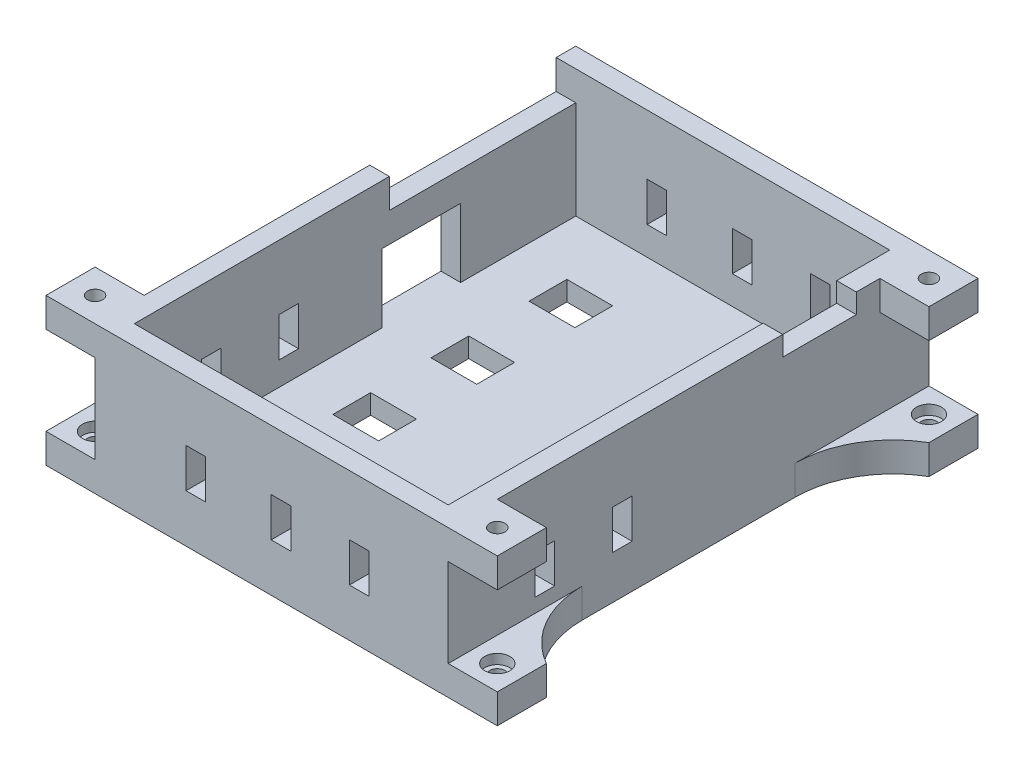
SolidWorks part; units mm, degrees
ref_plane "Спереди" through (0, 0, 0) normal (0, 0, 1) x (1, 0, 0)
ref_plane "Сверху" through (0, 0, 0) normal (0, 1, 0) x (1, 0, 0)
ref_plane "Справа" through (0, 0, 0) normal (1, 0, 0) x (0, 0, -1)
sketch "Sketch1" plane through (0, 0, 0) normal (0, 1, 0) x (1, 0, 0)
  line L1 (-13.614, 19.3684) -> (22.386, 19.3684)
  line L2 (-13.614, 19.3684) -> (-13.614, -29.6316)
  line L3 (-13.614, -29.6316) -> (22.386, -29.6316)
  line L4 (22.386, 19.3684) -> (22.386, -29.6316)
  dimension "D1" = 36
  dimension "D2" = 49
extrude "Boss-Extrude1" add sketch "Sketch1" along normal blind 2
sketch "Sketch2" plane through (0, 2, 0) normal (0, 1, 0) x (1, 0, 0)
  line L1 (-11.614, 17.3684) -> (20.386, 17.3684)
  line L2 (-11.614, 17.3684) -> (-11.614, -27.6316)
  line L3 (-11.614, -27.6316) -> (20.386, -27.6316)
  line L4 (20.386, 17.3684) -> (20.386, -27.6316)
  line L5 (-13.614, 19.3684) -> (22.386, 19.3684)
  line L6 (-13.614, 19.3684) -> (-13.614, -29.6316)
  line L7 (-13.614, -29.6316) -> (22.386, -29.6316)
  line L8 (22.386, 19.3684) -> (22.386, -29.6316)
  dimension "D1" = 2
  dimension "D2" = 2
  dimension "D3" = 2
  dimension "D4" = 2
extrude "Boss-Extrude2" add sketch "Sketch2" along normal blind 13
sketch "Sketch3" plane through (20.386, 0, 0) normal (-1, 0, 0) x (0, 0, 1)
  line L0 (27.6316, 15) -> (-17.3684, 15) construction
  line L1 (-11.9684, 15) -> (-4.4684, 15)
  line L2 (-11.9684, 15) -> (-11.9684, 13)
  line L3 (-11.9684, 13) -> (-4.4684, 13)
  line L4 (-4.4684, 15) -> (-4.4684, 13)
  line L5 (-17.3684, 15) -> (-17.3684, 2) construction
  dimension "D1" = 7.5
  dimension "D2" = 5.4
  dimension "D3" = 2
extrude "Cut-Extrude1" cut sketch "Sketch3" against normal through all and the other way blind 5
sketch "Sketch4" plane through (0, 0, 0) normal (0, -1, 0) x (1, 0, 0)
  line L0 (4.386, 29.6316) -> (4.386, -19.3684) construction
  line L1 (-13.614, 29.6316) -> (22.386, 29.6316) construction
  line L2 (22.386, -19.3684) -> (-13.614, -19.3684) construction
  line L3 (9.5173, 22.5248) -> (14.1877, 22.5248)
  line L4 (-6.4827, 22.5248) -> (-1.8123, 22.5248)
  line L5 (-6.4827, 22.5248) -> (-6.4827, 18.6717)
  line L6 (-6.4827, 18.6717) -> (-1.8123, 18.6717)
  line L7 (-1.8123, 22.5248) -> (-1.8123, 18.6717)
  line L8 (14.1877, 22.5248) -> (14.1877, 18.6717)
  line L9 (9.5173, 18.6717) -> (14.1877, 18.6717)
  line L10 (9.5173, 22.5248) -> (9.5173, 18.6717)
  line L11 (9.5173, 12.5248) -> (14.1877, 12.5248)
  line L12 (14.1877, 12.5248) -> (14.1877, 8.6717)
  line L13 (9.5173, 8.6717) -> (14.1877, 8.6717)
  line L14 (9.5173, 12.5248) -> (9.5173, 8.6717)
  line L15 (9.5173, 2.5248) -> (14.1877, 2.5248)
  line L16 (14.1877, 2.5248) -> (14.1877, -1.3283)
  line L17 (9.5173, -1.3283) -> (14.1877, -1.3283)
  line L18 (9.5173, 2.5248) -> (9.5173, -1.3283)
  line L19 (9.5173, -7.4752) -> (14.1877, -7.4752)
  line L20 (14.1877, -7.4752) -> (14.1877, -11.3283)
  line L21 (9.5173, -11.3283) -> (14.1877, -11.3283)
  line L22 (9.5173, -7.4752) -> (9.5173, -11.3283)
  line L23 (-6.4827, 12.5248) -> (-1.8123, 12.5248)
  line L24 (-1.8123, 12.5248) -> (-1.8123, 8.6717)
  line L25 (-6.4827, 8.6717) -> (-1.8123, 8.6717)
  line L26 (-6.4827, 12.5248) -> (-6.4827, 8.6717)
  line L27 (-6.4827, 2.5248) -> (-1.8123, 2.5248)
  line L28 (-1.8123, 2.5248) -> (-1.8123, -1.3283)
  line L29 (-6.4827, -1.3283) -> (-1.8123, -1.3283)
  line L30 (-6.4827, 2.5248) -> (-6.4827, -1.3283)
  line L31 (-6.4827, -7.4752) -> (-1.8123, -7.4752)
  line L32 (-1.8123, -7.4752) -> (-1.8123, -11.3283)
  line L33 (-6.4827, -11.3283) -> (-1.8123, -11.3283)
  line L34 (-6.4827, -7.4752) -> (-6.4827, -11.3283)
  dimension "D1" = 2
  dimension "D2" = 4
extrude "Cut-Extrude2" cut sketch "Sketch4" against normal through all
sketch "Sketch10" plane through (0, 15, 0) normal (0, 1, 0) x (1, 0, 0)
  line L0 (-13.614, 19.3684) -> (-13.614, -29.6316) construction
  line L1 (-11.614, 17.3684) -> (-13.614, 17.3684)
  line L2 (-11.614, 17.3684) -> (-11.614, -1.6316)
  line L3 (-11.614, -1.6316) -> (-13.614, -1.6316)
  line L4 (-13.614, 17.3684) -> (-13.614, -1.6316)
  dimension "D1" = 19
extrude "Cut-Extrude6" cut sketch "Sketch10" against normal blind 3
sketch "Sketch11" plane through (-13.614, 0, 0) normal (-1, 0, 0) x (0, 0, 1)
  line L0 (-19.3684, 0) -> (29.6316, 0) construction
  line L1 (-5.6344, 2) -> (2.3656, 2)
  line L2 (-5.6344, 2) -> (-5.6344, 9)
  line L3 (-5.6344, 9) -> (2.3656, 9)
  line L4 (2.3656, 2) -> (2.3656, 9)
  dimension "D1" = 7
  dimension "D2" = 8
  dimension "D3" = 2
extrude "Cut-Extrude7" cut sketch "Sketch11" against normal blind 2
sketch "Sketch12" plane through (-13.614, 0, 0) normal (-1, 0, 0) x (0, 0, 1)
  line L1 (-19.3684, 0) -> (-14.3684, 0)
  line L2 (-19.3684, 0) -> (-19.3684, 3)
  line L3 (-19.3684, 3) -> (-14.3684, 3)
  line L4 (-14.3684, 0) -> (-14.3684, 3)
  line L5 (29.6316, 15) -> (24.6316, 15)
  line L6 (29.6316, 15) -> (29.6316, 12)
  line L7 (29.6316, 12) -> (24.6316, 12)
  line L8 (24.6316, 15) -> (24.6316, 12)
  line L9 (29.6316, 0) -> (24.6316, 0)
  line L10 (29.6316, 0) -> (29.6316, 3)
  line L11 (29.6316, 3) -> (24.6316, 3)
  line L12 (24.6316, 0) -> (24.6316, 3)
  dimension "D1" = 5
  dimension "D2" = 3
extrude "Boss-Extrude3" add sketch "Sketch12" along normal blind 5
sketch "Sketch13" plane through (22.386, 0, 0) normal (1, 0, 0) x (0, 0, -1)
  line L1 (19.3684, 0) -> (14.3684, 0)
  line L2 (19.3684, 0) -> (19.3684, 3)
  line L3 (19.3684, 3) -> (14.3684, 3)
  line L4 (14.3684, 0) -> (14.3684, 3)
  line L9 (-29.6316, 15) -> (-24.6316, 15)
  line L10 (-29.6316, 15) -> (-29.6316, 12)
  line L11 (-29.6316, 12) -> (-24.6316, 12)
  line L12 (-24.6316, 15) -> (-24.6316, 12)
  line L13 (-29.6316, 0) -> (-24.6316, 0)
  line L14 (-29.6316, 0) -> (-29.6316, 3)
  line L15 (-29.6316, 3) -> (-24.6316, 3)
  line L16 (-24.6316, 0) -> (-24.6316, 3)
  line L17 (19.3684, 15) -> (14.3684, 15)
  line L18 (19.3684, 15) -> (19.3684, 12)
  line L19 (19.3684, 12) -> (14.3684, 12)
  line L20 (14.3684, 15) -> (14.3684, 12)
  dimension "D1" = 3
  dimension "D2" = 5
extrude "Boss-Extrude4" add sketch "Sketch13" along normal blind 5
sketch "Sketch14" plane through (0, 0, 0) normal (0, -1, 0) x (1, 0, 0)
  line L0 (27.386, -19.3684) -> (-18.614, -19.3684) construction
  line L1 (27.386, -14.3684) -> (27.386, -19.3684) construction
  line L3 (-18.614, -19.3684) -> (-18.614, -14.3684) construction
  line L5 (-18.614, 29.6316) -> (27.386, 29.6316) construction
  circle A0 centre (24.886, -16.8684) radius 0.775
  circle A1 centre (-16.114, -16.8684) radius 0.775
  circle A2 centre (-16.114, 27.1316) radius 0.775
  circle A3 centre (24.886, 27.1316) radius 0.775
  dimension "D6" = 1.55
  dimension "D1" = 2.5
  dimension "D2" = 2.5
  dimension "D3" = 2.5
  dimension "D4" = 2.5
  dimension "D5" = 2.5
extrude "Cut-Extrude8" cut sketch "Sketch14" against normal through all
sketch "Sketch15" plane through (0, 3, 0) normal (0, 1, 0) x (1, 0, 0)
  circle A0 centre (24.886, 16.8684) radius 1.275
  circle A1 centre (24.886, -27.1316) radius 1.275
  circle A2 centre (-16.114, -27.1316) radius 1.275
  circle A3 centre (-16.114, 16.8684) radius 1.275
  dimension "D1" = 2.55
extrude "Cut-Extrude9" cut sketch "Sketch15" against normal blind 1
sketch "Sketch16" plane through (0, 12, 0) normal (0, -1, 0) x (1, 0, 0)
  circle A0 centre (-16.114, 27.1316) radius 1.275
  circle A1 centre (24.886, 27.1316) radius 1.275
  circle A2 centre (24.886, -16.8684) radius 1.275
  dimension "D1" = 2.55
extrude "Cut-Extrude10" cut sketch "Sketch16" against normal blind 1
fillet "Fillet2" radius 10 4 edges at (-13.614, 1.5, -14.3684) (22.386, 1.5, -14.3684) (22.386, 1.5, 24.6316) (-13.614, 1.5, 24.6316)
sketch "Sketch17" plane through (0, 0, 29.6316) normal (0, 0, 1) x (1, 0, 0)
  line L1 (-4.3402, 8.8945) -> (-2.3402, 8.8945)
  line L2 (-4.3402, 8.8945) -> (-4.3402, 4.8945)
  line L3 (-4.3402, 4.8945) -> (-2.3402, 4.8945)
  line L4 (-2.3402, 8.8945) -> (-2.3402, 4.8945)
  line L5 (4.3432, 8.8945) -> (6.3432, 8.8945)
  line L6 (4.3432, 8.8945) -> (4.3432, 4.8945)
  line L7 (4.3432, 4.8945) -> (6.3432, 4.8945)
  line L8 (6.3432, 8.8945) -> (6.3432, 4.8945)
  line L9 (12.3095, 8.8945) -> (14.3095, 8.8945)
  line L10 (12.3095, 8.8945) -> (12.3095, 4.8945)
  line L11 (12.3095, 4.8945) -> (14.3095, 4.8945)
  line L12 (14.3095, 8.8945) -> (14.3095, 4.8945)
  dimension "D1" = 2
  dimension "D2" = 4
extrude "Cut-Extrude11" cut sketch "Sketch17" against normal through all
sketch "Sketch18" plane through (-13.614, 0, 0) normal (-1, 0, 0) x (0, 0, 1)
  line L1 (10.8938, 8.4242) -> (12.8938, 8.4242)
  line L2 (10.8938, 8.4242) -> (10.8938, 4.4242)
  line L3 (10.8938, 4.4242) -> (12.8938, 4.4242)
  line L4 (12.8938, 8.4242) -> (12.8938, 4.4242)
  line L5 (18.7843, 8.4242) -> (20.7843, 8.4242)
  line L6 (18.7843, 8.4242) -> (18.7843, 4.4242)
  line L7 (18.7843, 4.4242) -> (20.7843, 4.4242)
  line L8 (20.7843, 8.4242) -> (20.7843, 4.4242)
  dimension "D1" = 2
  dimension "D2" = 4
extrude "Cut-Extrude12" cut sketch "Sketch18" against normal through all
sketch "Sketch19" plane through (0, 15, 0) normal (0, 1, 0) x (1, 0, 0)
  line L0 (20.386, 17.3684) -> (-13.614, 17.3684) construction
  line L1 (-13.614, 19.3684) -> (23.4688, 19.3684)
  line L2 (-13.614, 19.3684) -> (-13.614, 17.3684)
  line L3 (-13.614, 17.3684) -> (23.4688, 17.3684)
  line L4 (23.4688, 19.3684) -> (23.4688, 17.3684)
extrude "Cut-Extrude13" cut sketch "Sketch19" against normal blind 2
sketch "Sketch20" plane through (0, 13, 0) normal (0, 1, 0) x (1, 0, 0)
  line L1 (-13.614, 19.3684) -> (23.4688, 19.3684)
  line L2 (-13.614, 19.3684) -> (-13.614, 17.3684)
  line L3 (-13.614, 17.3684) -> (23.4688, 17.3684)
  line L4 (23.4688, 19.3684) -> (23.4688, 17.3684)
extrude "Boss-Extrude5" add sketch "Sketch20" along normal blind 2
sketch "Sketch21" plane through (0, 15, 0) normal (0, 1, 0) x (1, 0, 0)
  line L0 (-18.614, -29.6316) -> (27.386, -29.6316) construction
  line L1 (-11.614, -1.6316) -> (-13.614, -1.6316)
  line L2 (-11.614, -1.6316) -> (-11.614, -29.6316)
  line L3 (-11.614, -29.6316) -> (-13.614, -29.6316)
  line L4 (-13.614, -1.6316) -> (-13.614, -29.6316)
extrude "Cut-Extrude14" cut sketch "Sketch21" against normal blind 2
sketch "Sketch22" plane through (0, 13, 0) normal (0, 1, 0) x (1, 0, 0)
  line L1 (-13.614, -1.6316) -> (-11.614, -1.6316)
  line L2 (-13.614, -1.6316) -> (-13.614, -29.6316)
  line L3 (-13.614, -29.6316) -> (-11.614, -29.6316)
  line L4 (-11.614, -1.6316) -> (-11.614, -29.6316)
extrude "Boss-Extrude6" add sketch "Sketch22" along normal blind 2
sketch "Sketch23" plane through (0, 15, 0) normal (0, 1, 0) x (1, 0, 0)
  line L0 (-18.614, -29.6316) -> (27.386, -29.6316) construction
  line L1 (20.386, 4.4684) -> (22.386, 4.4684)
  line L2 (20.386, 4.4684) -> (20.386, -29.6316)
  line L3 (20.386, -29.6316) -> (22.386, -29.6316)
  line L4 (22.386, 4.4684) -> (22.386, -29.6316)
extrude "Cut-Extrude16" cut sketch "Sketch23" against normal blind 1.5
sketch "Sketch24" plane through (0, 13.5, 0) normal (0, 1, 0) x (1, 0, 0)
  line L0 (20.386, -29.6316) -> (22.386, -29.6316) construction
  line L1 (20.386, 4.4684) -> (22.386, 4.4684)
  line L2 (20.386, 4.4684) -> (20.386, -29.6316)
  line L3 (20.386, -29.6316) -> (22.386, -29.6316)
  line L4 (22.386, 4.4684) -> (22.386, -29.6316)
extrude "Boss-Extrude7" add sketch "Sketch24" along normal blind 1.5
